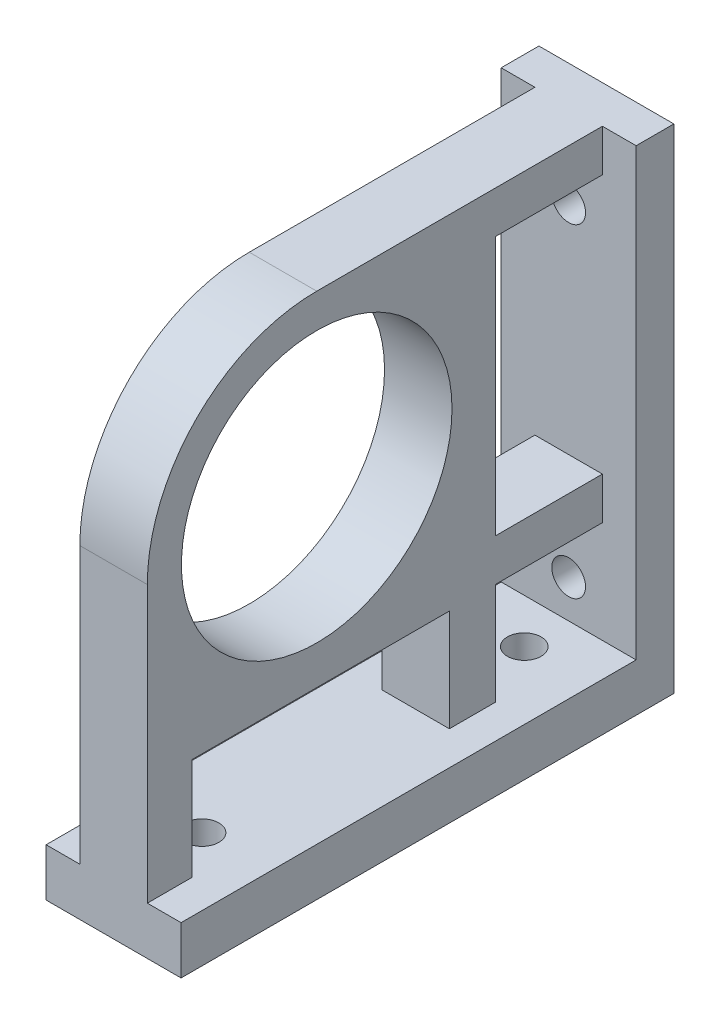
SolidWorks part; units mm, degrees
ref_plane "Front Plane" through (0, 0, 0) normal (0, 0, 1) x (1, 0, 0)
ref_plane "Top Plane" through (0, 0, 0) normal (0, 1, 0) x (1, 0, 0)
ref_plane "Right Plane" through (0, 0, 0) normal (1, 0, 0) x (0, 0, -1)
sketch "Sketch1" plane through (0, 0, 0) normal (1, 0, 0) x (0, 0, -1)
  line L11 (0, 31.8822) -> (31.8822, 31.8822)
  line L12 (31.8822, 31.8822) -> (60.8746, 31.8822)
  line L16 (60.8746, 31.8822) -> (60.8746, -60.96)
  line L17 (-31.8822, 0) -> (-31.8822, -60.96)
  line L18 (60.8746, -60.96) -> (-31.8822, -60.96)
  circle A1 centre (0, 0) radius 25.4635
  arc A3 (0, 31.8822) -> (-31.8822, 0) centre (0, 0) ccw
extrude "Boss-Extrude1" add sketch "Sketch1" along normal blind 12.7
sketch "Sketch8" plane through (12.7, 0, 0) normal (1, 0, 0) x (0, 0, -1)
  line L0 (-31.8822, -60.96) -> (60.8746, -60.96) construction
  line L1 (60.8746, 31.8822) -> (53.7706, 31.8822)
  line L2 (60.8746, 31.8822) -> (60.8746, -60.96)
  line L3 (60.8746, -60.96) -> (53.7706, -60.96)
  line L4 (53.7706, 31.8822) -> (53.7706, -51.9379)
  line L5 (-31.8822, 0) -> (-31.8822, -60.96) construction
  line L6 (53.7706, -60.96) -> (-31.8822, -60.96)
  line L8 (53.7706, -51.9379) -> (-31.8822, -51.9379)
  line L9 (-31.8822, -60.96) -> (-31.8822, -51.9379)
extrude "Boss-Extrude2" add sketch "Sketch8" along normal blind 6.35 and the other way blind 19.05
sketch "Sketch2" plane through (0, 0, 0) normal (0, 1, 0) x (1, 0, 0)
  circle A0 centre (6.35, 0) radius 3.175
extrude "Cut-Extrude1" [suppressed] cut sketch "Sketch2" along normal through all
sketch "Sketch10" plane through (0, 0, 31.8822) normal (0, 0, 1) x (1, 0, 0)
  line L0 (12.7, 0) -> (0, 0) construction
  circle A0 centre (6.35, 0) radius 3.175
extrude "Cut-Extrude6" [suppressed] cut sketch "Sketch10" against normal blind 8.128
fillet "Fillet1" [suppressed] radius 2.54
mirror "Mirror1" [suppressed] about plane through (0, 0, 0) normal (0, 0, 1)
fillet "Fillet2" [suppressed] radius 5.08
sketch "Sketch4" plane through (0, 0, 0) normal (-1, 0, 0) x (0, 0, 1)
  line L4 (-53.7706, 23.9633) -> (-33.6922, 23.9633)
  line L5 (-33.6922, 23.9633) -> (-33.6922, -24.8177)
  line L6 (-24.9665, -32.7419) -> (23.4543, -32.7419)
  line L7 (23.4543, -32.7419) -> (23.4543, -51.9379)
  line L8 (23.4543, -51.9379) -> (-24.9665, -51.9379)
  line L9 (-53.7706, -51.9379) -> (-53.7706, -32.7419)
  line L10 (-33.6922, -32.7419) -> (-33.6922, -51.9379)
  line L11 (-24.9665, -51.9379) -> (-24.9665, -32.7419)
  line L12 (-33.6922, -51.9379) -> (-53.7706, -51.9379)
  line L13 (-33.6922, -32.7419) -> (-53.7706, -32.7419)
  line L14 (-33.6922, -24.8177) -> (-53.7706, -24.8177)
  line L15 (-53.7706, -24.8177) -> (-53.7706, 23.9633)
extrude "Cut-Extrude2" cut sketch "Sketch4" against normal blind 26.162
sketch "Sketch5" plane through (0, 0, -60.8746) normal (0, 0, -1) x (-1, 0, 0)
  circle A0 centre (-6.35, 16.187) radius 3.175
  circle A1 centre (-6.35, -44.7886) radius 3.175
extrude "Cut-Extrude3" cut sketch "Sketch5" against normal blind 11.43
sketch "Sketch6" plane through (0, -60.96, 0) normal (0, -1, 0) x (1, 0, 0)
  circle A0 centre (6.35, 15.24) radius 3.175
  circle A1 centre (6.35, -45.4106) radius 3.175
extrude "Cut-Extrude4" cut sketch "Sketch6" against normal blind 11.43
sketch "Sketch9" plane through (0, 0, 0) normal (-1, 0, 0) x (0, 0, 1)
  line L1 (-33.6922, -24.8177) -> (-71.3105, -24.8177)
  line L2 (-33.6922, -24.8177) -> (-33.6922, 42.9585)
  line L3 (-33.6922, 42.9585) -> (-71.3105, 42.9585)
  line L4 (-71.3105, -24.8177) -> (-71.3105, 42.9585)
extrude "Cut-Extrude5" [suppressed] cut sketch "Sketch9" against normal blind 41.656 and the other way blind 46.736
fillet "Fillet3" [suppressed] radius 33.02
sketch "Sketch11" plane through (0, 0, 0) normal (-1, 0, 0) x (0, 0, 1)
  circle A0 centre (0, 0) radius 25.4
extrude "Cut-Extrude7" [suppressed] cut sketch "Sketch11" against normal blind 20.828
